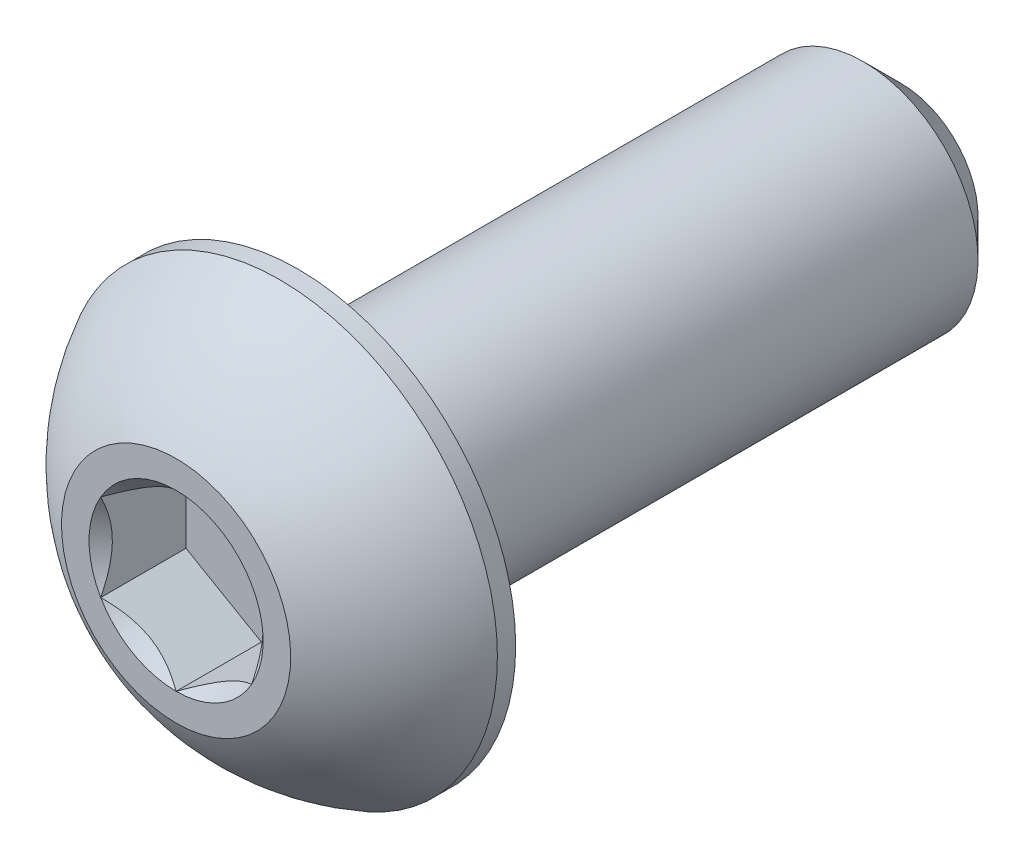
SolidWorks part; units mm, degrees
ref_plane "Front" through (0, 0, 0) normal (0, 0, 1) x (1, 0, 0)
ref_plane "Top" through (0, 0, 0) normal (0, 1, 0) x (1, 0, 0)
ref_plane "Right" through (0, 0, 0) normal (1, 0, 0) x (0, 0, -1)
sketch "Sketch1" plane through (0, 0, 0) normal (1, 0, 0) x (0, 0, -1)
  line L2 (2.5654, 2.413) -> (15.2654, 2.413)
  line L3 (15.2654, 2.413) -> (15.2654, 0)
  line L4 (15.2654, 0) -> (2.5654, 0)
  line L6 (2.1806, 4.5847) -> (2.5654, 4.5847) construction
  line L7 (15.2654, 2.413) -> (15.2654, -2.413) construction
  line L8 (0, 0) -> (2.5654, 0) construction
  line L9 (2.5654, 4.5847) -> (2.5654, -4.5847) construction
  line L11 (2.5654, 2.413) -> (2.5654, 0)
  line L13 (0, 1.5875) -> (0, -1.5875) construction
  line L14 (0, 1.5875) -> (0, 2.413) construction
  arc A3 (0, 2.413) -> (2.1806, 4.5847) centre (4.5749, 0) cw construction
  dimension "D1" = 0.3848
revolve "Revolve1" add sketch "Sketch1" angle 360 mid plane about L4
sketch "Sketch3" plane through (0, 0, -15.2654) normal (0, 0, -1) x (-1, 0, 0)
  circle A0 centre (0, 0) radius 2.413
curve "Helix/Spiral1" pitch 1.0583 height 13.7583 turns 13
sketch "Sketch2" plane through (0, 0, 0) normal (1, 0, 0) x (0, 0, -1)
  line L0 (15.2654, 2.413) -> (16.1914, 2.413)
  line L1 (16.1914, 2.413) -> (15.7946, 1.7256)
  line L2 (15.7946, 1.7256) -> (15.6623, 1.7256)
  line L3 (15.6623, 1.7256) -> (15.2654, 2.413)
  line L4 (15.4638, 2.0693) -> (15.993, 2.0693) construction
  dimension "D1" = 60
  dimension "D2" = 0.1323
  dimension "D3" = 0.5292
chamfer "Chamfer1" distance 0.7937 angle 45 1 edges at (0, 2.413, -15.2654)
sweep "Cut-Sweep1" [suppressed] cut profiles "Sketch2" path "Helix/Spiral1"
sketch "Sketch7" plane through (0, 0, 0) normal (1, 0, 0) x (0, 0, -1)
  line L6 (2.1806, 4.5847) -> (2.5654, 4.5847) construction
  line L8 (0, 0) -> (2.5654, 0) construction
  line L11 (2.5654, 4.5847) -> (2.5654, -4.5847) construction
  line L12 (2.1806, 4.5847) -> (2.5654, 4.5847)
  line L13 (0, 0) -> (2.5654, 0)
  line L14 (0, 1.5875) -> (0, -1.5875) construction
  line L15 (2.5654, 4.5847) -> (2.5654, 0)
  line L16 (0, 2.413) -> (0, 0)
  arc A2 (2.1806, 4.5847) -> (0, 2.413) centre (4.5749, 0) ccw construction
  arc A3 (2.1806, 4.5847) -> (0, 2.413) centre (4.5749, 0) ccw
revolve "Revolve2" add sketch "Sketch7" angle 360 mid plane about L13
sketch "Sketch5" plane through (0, 0, 0) normal (0, 0, 1) x (1, 0, 0)
  line L1 (1.5875, -0.9165) -> (1.5875, 0.9165)
  line L2 (1.5875, 0.9165) -> (0, 1.8331)
  line L3 (0, 1.8331) -> (-1.5875, 0.9165)
  line L4 (-1.5875, 0.9165) -> (-1.5875, -0.9165)
  line L5 (-1.5875, -0.9165) -> (0, -1.8331)
  line L6 (0, -1.8331) -> (1.5875, -0.9165)
  circle A0 centre (0, 0) radius 1.5875 construction
extrude "Cut-Extrude2" cut sketch "Sketch5" against normal blind 1.7958
sketch "Sketch6" plane through (0, 0, 0) normal (0, 0, 1) x (1, 0, 0)
  circle A0 centre (0, 0) radius 1.8331
extrude "Cut-Extrude3" cut sketch "Sketch6" against normal blind 1.7958 draft 45
sketch "Sketch9" [suppressed] plane through (0, 0, -5.0546) normal (0, 0, 1) x (1, 0, 0)
  circle A2 centre (0, 0) radius 4.7625
extrude "Boss-Extrude2" [suppressed] add sketch "Sketch9" against normal offset from surface (12.7 mm away) 31.75
sketch "Sketch10" plane through (0, 0, 0) normal (1, 0, 0) x (0, 0, -1)
  line L0 (15.2654, 2.413) -> (15.2654, -2.413) construction
  point P0 (13.6779, -2.413)
  dimension "D1" = 1.5875
equation "\"D3@Helix/Spiral1\" = \"Lg@Sketch1\" + \"D4@Helix/Spiral1\""
equation "\"D2@Sketch2\" = \"D4@Helix/Spiral1\" * .125"
equation "\"D3@Sketch2\" = \"D4@Helix/Spiral1\" * .5"
equation "\"D1@Chamfer1\" = \"D4@Helix/Spiral1\" * .75"
equation "\"D1@Cut-Extrude2\" = \"Head Ht@Sketch1\" * .7"
equation "\"D1@Sketch1\" = \"Head Ht@Sketch1\" * .15"
equation "\"D1@Sketch10\" = \"D4@Helix/Spiral1\" * 1.5"
equation "\"D1@Cut-Extrude3\" = \"D1@Cut-Extrude2\""
